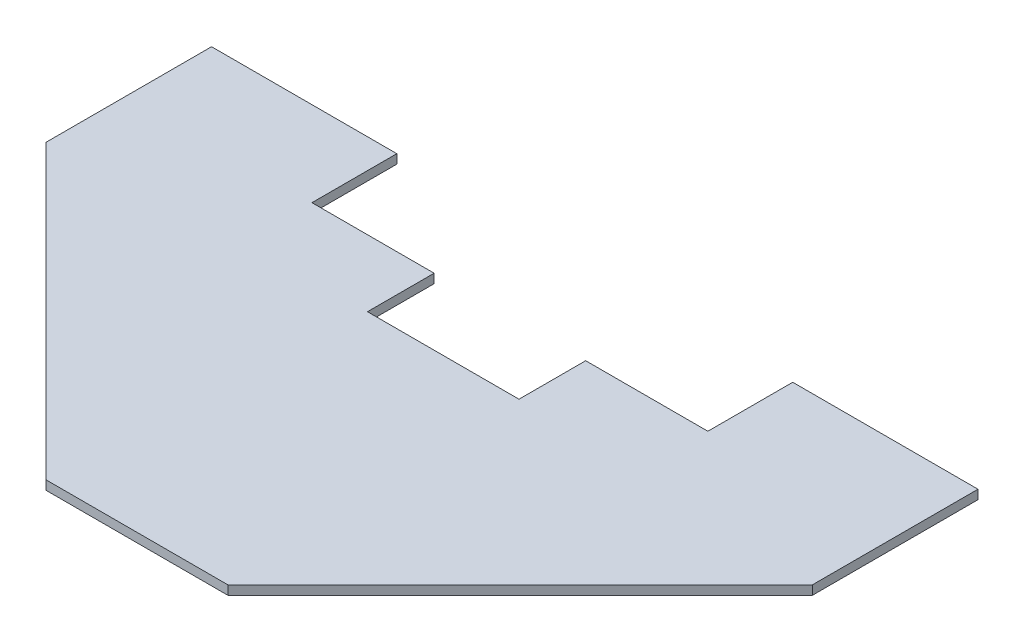
SolidWorks part; units mm, degrees
material "AISI 1020"
ref_plane "Спереди" through (0, 0, 0) normal (0, 0, 1) x (1, 0, 0)
ref_plane "Сверху" through (0, 0, 0) normal (0, 1, 0) x (1, 0, 0)
ref_plane "Справа" through (0, 0, 0) normal (1, 0, 0) x (0, 0, -1)
sketch "Эскиз1" plane through (0, 0, 0) normal (0, 1, 0) x (1, 0, 0)
  line L2 (0, -202.132) -> (60, -202.132)
  line L3 (60, -202.132) -> (252.882, -9.25)
  line L4 (252.882, -9.25) -> (252.882, 100)
  line L5 (252.882, 100) -> (130.6264, 100)
  line L6 (130.6264, 100) -> (130.6264, 44)
  line L7 (130.6264, 44) -> (50, 44)
  line L8 (50, 44) -> (50, 0)
  line L17 (50, -4120.3489) -> (50, 0) construction
  line L18 (50, 6) -> (50, 94) construction
  line L19 (116.3889, 44) -> (54.2376, 44) construction
  line L20 (120.6264, 91) -> (120.6264, 47) construction
  line L23 (0, 0) -> (0, -202.132) construction
  line L24 (0, 0) -> (0, -202.132)
  line L25 (85.3132, 100) -> (2439.6868, 100) construction
  line L26 (0, 148.4) -> (0, 51.6) construction
  line L27 (925, 0.75) -> (-275, 0.75) construction
  line L29 (0, 0) -> (50, 0)
  dimension "D1" = 150
  dimension "D2" = 10
  dimension "D3" = 10
  dimension "D4" = 10
  dimension "D5" = 45
base flange "Базовая кромка1" sketch "Эскиз1" thickness 6 reverse thickness direction no parameters "D1"=0.75
mirror "Зеркальное отражение1" about plane through (0, -6, 0) normal (-1, 0, 0) of bodies 103
sketch "Сгиб-Линии1" plane through (0, 0, 0) normal (0, 1, 0) x (1, 0, 0)
sketch "Граничная рамка1" plane through (0, 0, 0) normal (0, 1, 0) x (1, 0, 0)
sheet metal parameters "Листовой металл3" thickness 6 parameters "D1"=0.75
flat pattern "Развертка3" [suppressed]
sketch "Сгиб-Линии2" plane through (0, 0, 0) normal (0, 1, 0) x (1, 0, 0)
sketch "Граничная рамка2" [suppressed] plane through (0, 0, 0) normal (0, 1, 0) x (1, 0, 0)
sheet metal parameters "Листовой металл4" thickness 6 parameters "D1"=0.75
flat pattern "Развертка4"
sketch "Сгиб-Линии3" plane through (0, 0, 0) normal (0, 1, 0) x (1, 0, 0)
sketch "Граничная рамка3" [suppressed] plane through (0, 0, 0) normal (0, 1, 0) x (1, 0, 0)
